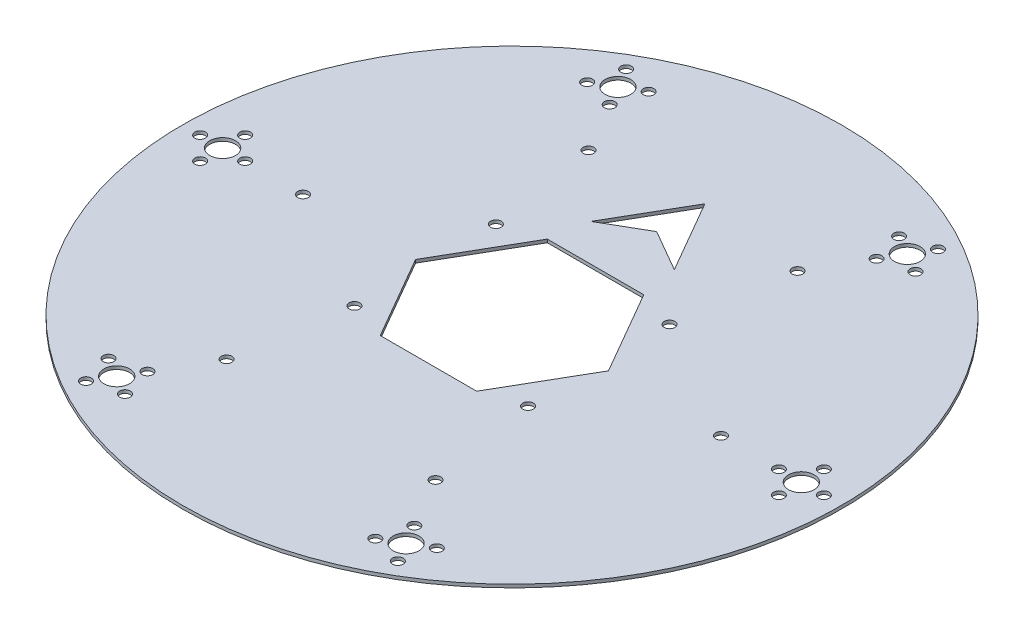
SolidWorks part; units mm, degrees
ref_plane "前视基准面" through (0, 0, 0) normal (0, 0, 1) x (1, 0, 0)
ref_plane "上视基准面" through (0, 0, 0) normal (0, 1, 0) x (1, 0, 0)
ref_plane "右视基准面" through (0, 0, 0) normal (1, 0, 0) x (0, 0, -1)
sketch "草图1" plane through (0, 0, 0) normal (0, 1, 0) x (1, 0, 0)
  line L0 (-12.9904, 37.5) -> (0, 60)
  line L1 (30, 0) -> (15, 25.9808)
  line L2 (15, 25.9808) -> (-15, 25.9808)
  line L3 (-15, 25.9808) -> (-30, 0)
  line L4 (-30, 0) -> (-15, -25.9808)
  line L5 (-15, -25.9808) -> (15, -25.9808)
  line L6 (15, -25.9808) -> (30, 0)
  line L7 (0, 60) -> (12.9904, 37.5)
  line L8 (12.9904, 37.5) -> (0, 45)
  line L9 (0, 45) -> (-12.9904, 37.5)
  circle A0 centre (0, 0) radius 102.5
  circle A1 centre (0, 0) radius 90 construction
  circle A2 centre (0, 0) radius 30 construction
  point P16 (0, 25.9808)
  dimension "D1" = 205
  dimension "D2" = 180
  dimension "D3" = 60
  dimension "D4" = 120
  dimension "D5" = 60
  dimension "D6" = 15
base flange "基体-法兰1" sketch "草图1" thickness 1 reverse thickness direction no parameters "D1"=0.7366
hole_wizard "Ø8.0 (8) 直径孔1" positions "草图6" profile "草图7" hole size "Ø8.0" standard "GB" end condition through all
sketch "草图6" plane through (0, 0, 0) normal (0, 1, 0) x (1, 0, 0)
  line L0 (0, 0) -> (-15, 25.9808) construction
  line L1 (-15, 25.9808) -> (-45, 77.9423) construction
  circle A0 centre (0, 0) radius 90 construction
  point P0 (-45, 77.9423)
  dimension "D1" = 180
sketch "草图7" plane through (-45, 0, -77.9423) normal (1, 0, 0) x (0, 0, 1)
  line L0 (0, 0) -> (0, 1)
  line L1 (0, 1) -> (4, 1)
  line L2 (4, 1) -> (4, 0)
  line L5 (4, 0) -> (0, 0)
  line L11 (0, -6.35) -> (0, 107.95) construction
  dimension "通孔孔直径" = 8
  dimension "通孔孔深度" = 1
pattern_circular "阵列(圆周)1" count 6 over 360 about axis through (0, 0, 0) along (0, 1, 0) of "Ø8.0 (8) 直径孔1"
hole_wizard "Ø3.3 (3.3) 直径孔1" positions "草图8" profile "草图9" hole size "Ø3.3" standard "GB" end condition through all
sketch "草图8" plane through (0, 0, 0) normal (0, 1, 0) x (1, 0, 0)
  line L0 (0, 0) -> (-59.2583, 102.6384) construction
  line L7 (0, 0) -> (108.7797, 0) construction
  line L12 (0, 0) -> (-117.5265, 0) construction
  line L15 (0, 0) -> (-62.0625, -107.4954) construction
  line L18 (0, 0) -> (63.188, -109.4448) construction
  line L23 (0, 0) -> (61.5554, 106.617) construction
  line L24 (-53.7071, 72.9152) -> (-38.2714, 81.827) construction
  line L25 (35.6472, 83.3421) -> (53.1426, 73.2412) construction
  line L26 (-56.4806, -71.314) -> (-34.348, -84.0922) construction
  line L27 (36.8811, -82.6297) -> (53.0011, -73.3229) construction
  circle A2 centre (-45, 77.9423) radius 7 construction
  circle A3 centre (45, 77.9423) radius 7 construction
  circle A4 centre (90, 0) radius 7 construction
  circle A5 centre (45, -77.9423) radius 7 construction
  circle A6 centre (-45, -77.9423) radius 7 construction
  circle A7 centre (-90, 0) radius 7 construction
  point P2 (-48.5, 84.0045)
  point P75 (-51.0622, 74.4423)
  point P77 (-41.5, 71.8801)
  point P79 (-38.9378, 81.4423)
  point P98 (48.5, 84.0045)
  point P100 (38.9378, 81.4423)
  point P102 (51.0622, 74.4423)
  point P104 (41.5, 71.8801)
  point P107 (90, 7)
  point P109 (90, -7)
  point P111 (97, 0)
  point P113 (83, 0)
  point P115 (-83, 0)
  point P117 (-97, 0)
  point P119 (-90, 7)
  point P121 (-90, -7)
  point P130 (-48.5, -84.0045)
  point P132 (-38.9378, -81.4423)
  point P134 (-41.5, -71.8801)
  point P136 (-51.0622, -74.4423)
  point P145 (51.0622, -74.4423)
  point P147 (41.5, -71.8801)
  point P149 (38.9378, -81.4423)
  point P151 (48.5, -84.0045)
  dimension "D1" = 14
  dimension "D2" = 6
sketch "草图9" plane through (-48.5, 0, -84.0045) normal (1, 0, 0) x (0, 0, 1)
  line L0 (0, 0) -> (0, 1)
  line L1 (0, 1) -> (1.65, 1)
  line L2 (1.65, 1) -> (1.65, 0)
  line L5 (1.65, 0) -> (0, 0)
  line L11 (0, -6.35) -> (0, 107.95) construction
  dimension "通孔孔直径" = 3.3
  dimension "通孔孔深度" = 1
hole_wizard "Ø3.3 (3.3) 直径孔2" positions "草图10" profile "草图11" hole size "Ø3.3" standard "GB" end condition through all
sketch "草图10" plane through (0, 0, 0) normal (0, 1, 0) x (1, 0, 0)
  line L1 (65, 0) -> (32.5, 56.2917) construction
  line L2 (32.5, 56.2917) -> (-32.5, 56.2917) construction
  line L3 (-32.5, 56.2917) -> (-65, 0) construction
  line L4 (-65, 0) -> (-32.5, -56.2917) construction
  line L5 (-32.5, -56.2917) -> (32.5, -56.2917) construction
  line L6 (32.5, -56.2917) -> (65, 0) construction
  circle A0 centre (0, 0) radius 65 construction
  point P5 (65, 0)
  point P6 (32.5, 56.2917)
  point P7 (-32.5, 56.2917)
  point P8 (-65, 0)
  point P9 (-32.5, -56.2917)
  point P10 (32.5, -56.2917)
  dimension "D1" = 130
sketch "草图11" plane through (32.5, 0, 56.2917) normal (1, 0, 0) x (0, 0, 1)
  line L0 (0, 0) -> (0, 1)
  line L1 (0, 1) -> (1.65, 1)
  line L2 (1.65, 1) -> (1.65, 0)
  line L5 (1.65, 0) -> (0, 0)
  line L11 (0, -6.35) -> (0, 107.95) construction
  dimension "通孔孔直径" = 3.3
  dimension "通孔孔深度" = 1
hole_wizard "Ø3.3 (3.3) 直径孔3" positions "草图14" profile "草图15" hole size "Ø3.3" standard "GB" end condition through all
sketch "草图14" plane through (0, 0, 0) normal (0, 1, 0) x (1, 0, 0)
  line L1 (-27, 22) -> (27, 22)
  line L2 (-27, 22) -> (-27, -22)
  line L3 (-27, -22) -> (27, -22)
  line L4 (27, 22) -> (27, -22)
  line L5 (-27, 22) -> (27, -22) construction
  line L6 (-27, -22) -> (27, 22) construction
  point P3 (0, 0)
  point P4 (27, -22)
  point P43 (-27, 22)
  point P44 (-27, -22)
  point P45 (27, 22)
  point P57 (0, 0)
  dimension "D1" = 44
  dimension "D2" = 54
sketch "草图15" plane through (0, 0, 0) normal (1, 0, 0) x (0, 0, 1)
  line L0 (0, 0) -> (0, 1)
  line L1 (0, 1) -> (1.65, 1)
  line L2 (1.65, 1) -> (1.65, 0)
  line L5 (1.65, 0) -> (0, 0)
  line L11 (0, -6.35) -> (0, 107.95) construction
  dimension "通孔孔直径" = 3.3
  dimension "通孔孔深度" = 1
sketch "折弯-线1" [suppressed] plane through (0, 0, 0) normal (0, 1, 0) x (1, 0, 0)
sketch "边界框1" [suppressed] plane through (0, 0, 0) normal (0, 1, 0) x (1, 0, 0)
sheet metal parameters "钣金1" thickness 1 parameters "D1"=0.7366
flat pattern "平板型式1" [suppressed]
sketch "折弯-线2" plane through (0, 0, 0) normal (0, 1, 0) x (1, 0, 0)
sketch3d "边界框2" [suppressed]
  line L0 (-100.1249, -99.8748, 0) -> (99.8749, -100.1248, 0) construction
  line L1 (-99.8749, 100.1249, 0) -> (100.1249, 99.8749, 0) construction
  line L2 (-100.1249, -99.8748, 0) -> (-99.8749, 100.1249, 0) construction
  line L3 (99.8749, -100.1248, 0) -> (100.1249, 99.8749, 0) construction
sheet metal parameters "钣金2" thickness 1 parameters "D1"=0.7366
flat pattern "平板型式1"
sketch "折弯-线2" plane through (0, 0, 0) normal (0, 1, 0) x (1, 0, 0)
sketch3d "边界框2" [suppressed]
  line L0 (100.1249, -99.8748, 0) -> (-99.8749, -100.1248, 0) construction
  line L1 (99.8749, 100.1249, 0) -> (-100.1249, 99.8749, 0) construction
  line L2 (100.1249, -99.8748, 0) -> (99.8749, 100.1249, 0) construction
  line L3 (-99.8749, -100.1248, 0) -> (-100.1249, 99.8749, 0) construction
sheet metal parameters "钣金3" thickness 1 parameters "D1"=0.7366
flat pattern "平板型式1"
sketch "折弯-线2" plane through (0, 0, 0) normal (0, 1, 0) x (1, 0, 0)
sketch3d "边界框2" [suppressed]
  line L0 (-102.6183, 102.3814, 0) -> (-102.3815, -102.6183, 0) construction
  line L1 (102.3814, 102.6183, 0) -> (102.6183, -102.3814, 0) construction
  line L2 (-102.6183, 102.3814, 0) -> (102.3814, 102.6183, 0) construction
  line L3 (-102.3815, -102.6183, 0) -> (102.6183, -102.3814, 0) construction
sheet metal parameters "钣金4" thickness 1 parameters "D1"=0.7366
flat pattern "平板型式1"
sketch "折弯-线2" plane through (0, 0, 0) normal (0, 1, 0) x (1, 0, 0)
sketch3d "边界框2" [suppressed]
  line L0 (-102.6183, 102.3814, 0) -> (-102.3815, -102.6183, 0) construction
  line L1 (102.3814, 102.6183, 0) -> (102.6183, -102.3814, 0) construction
  line L2 (-102.6183, 102.3814, 0) -> (102.3814, 102.6183, 0) construction
  line L3 (-102.3815, -102.6183, 0) -> (102.6183, -102.3814, 0) construction
sheet metal parameters "钣金7" thickness 1 parameters "D1"=0.7366
flat pattern "平板型式1"
sketch "折弯-线2" plane through (0, 0, 0) normal (0, 1, 0) x (1, 0, 0)
sketch3d "边界框2" [suppressed]
  line L0 (-102.6183, 102.3814, 0) -> (-102.3815, -102.6183, 0) construction
  line L1 (102.3814, 102.6183, 0) -> (102.6183, -102.3814, 0) construction
  line L2 (-102.6183, 102.3814, 0) -> (102.3814, 102.6183, 0) construction
  line L3 (-102.3815, -102.6183, 0) -> (102.6183, -102.3814, 0) construction
sheet metal parameters "钣金8" thickness 1 parameters "D1"=0.7366
flat pattern "平板型式1"
sketch "折弯-线2" plane through (0, 0, 0) normal (0, 1, 0) x (1, 0, 0)
sketch3d "边界框2" [suppressed]
  line L0 (-102.6183, 102.3814, 0) -> (-102.3815, -102.6183, 0) construction
  line L1 (102.3814, 102.6183, 0) -> (102.6183, -102.3814, 0) construction
  line L2 (-102.6183, 102.3814, 0) -> (102.3814, 102.6183, 0) construction
  line L3 (-102.3815, -102.6183, 0) -> (102.6183, -102.3814, 0) construction
